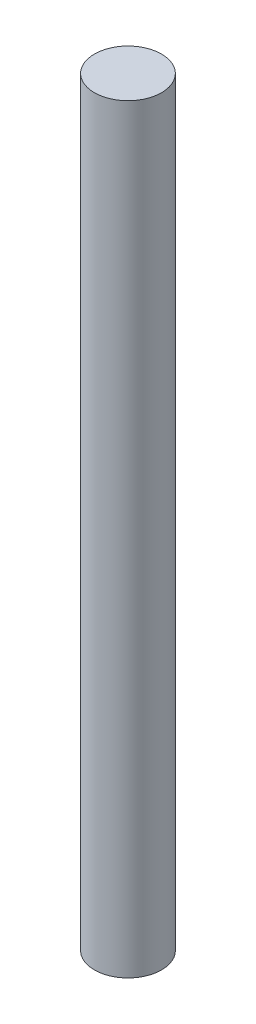
SolidWorks part; units mm, degrees
ref_plane "Front Plane" through (0, 0, 0) normal (0, 0, 1) x (1, 0, 0)
ref_plane "Top Plane" through (0, 0, 0) normal (0, 1, 0) x (1, 0, 0)
ref_plane "Right Plane" through (0, 0, 0) normal (1, 0, 0) x (0, 0, -1)
sketch "Sketch1" plane through (0, 0, 0) normal (0, 1, 0) x (1, 0, 0)
  circle A0 centre (0, 0) radius 1.5
  dimension "D1" = 3
extrude "Boss-Extrude1" add sketch "Sketch1" along normal blind 34
